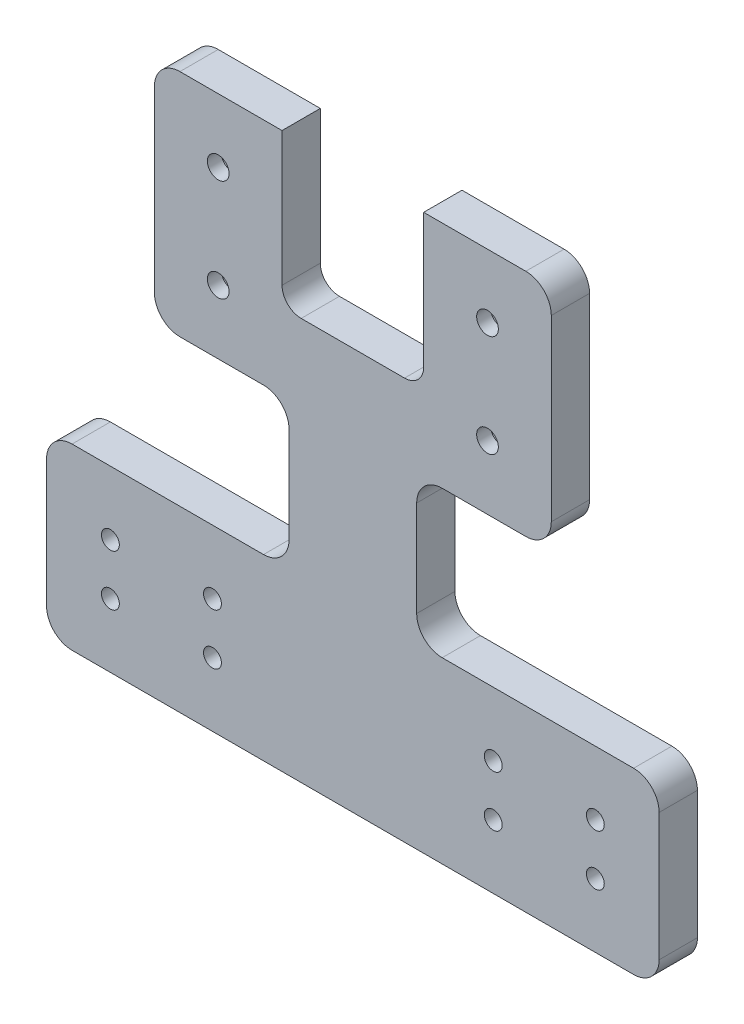
SolidWorks part; units mm, degrees
ref_plane "Front Plane" through (0, 0, 0) normal (0, 0, 1) x (1, 0, 0)
ref_plane "Top Plane" through (0, 0, 0) normal (0, 1, 0) x (1, 0, 0)
ref_plane "Right Plane" through (0, 0, 0) normal (1, 0, 0) x (0, 0, -1)
sketch "Sketch1" plane through (0, 0, 0) normal (0, 0, 1) x (1, 0, 0)
  line L0 (28.1, 15) -> (-28.1, 15) construction
  line L1 (-28.1, -15) -> (28.1, 15) construction
  line L2 (-28.1, 15) -> (-28.1, -15) construction
  line L3 (-28.1, -15) -> (28.1, -15) construction
  line L4 (-50, 20) -> (50, 20)
  line L5 (28.1, 15) -> (28.1, -15) construction
  line L6 (-50, 20) -> (-50, -80)
  line L7 (-50, -80) -> (50, -80)
  line L8 (50, 20) -> (50, -80)
  line L9 (-28.1, 15) -> (28.1, -15) construction
  line L10 (-50, 20) -> (50, -80) construction
  line L12 (-50, -80) -> (50, 20) construction
  dimension "D4" = 30
  dimension "D5" = 50
  dimension "D2" = 50
  dimension "D1" = 20
  dimension "D3" = 56.2
  dimension "D6" = 80
extrude "Boss-Extrude1" add sketch "Sketch1" along normal blind 6
sketch "Sketch2" plane through (0, 0, 0) normal (0, 0, 1) x (1, 0, 0)
  line L0 (28.1, 15) -> (-28.1, 15) construction
  line L1 (-28.1, -15) -> (28.1, 15) construction
  line L2 (-28.1, 15) -> (-28.1, -15) construction
  line L3 (-28.1, -15) -> (28.1, -15) construction
  line L4 (28.1, 15) -> (28.1, -15) construction
  line L5 (-28.1, 15) -> (28.1, -15) construction
  line L6 (-28.1, 0) -> (28.1, 0) construction
  line L14 (0, 15) -> (0, -15) construction
  circle A0 centre (21.1, -8) radius 2.9
  circle A1 centre (-21.1, 8) radius 2.9
  circle A2 centre (-21.1, -8) radius 2.9
  circle A4 centre (21.1, 8) radius 2.9
  dimension "D4" = 5.8
  dimension "D1" = 56.2
  dimension "D2" = 30
  dimension "D5" = 8
  dimension "D6" = 21.1
extrude "Cut-Extrude1" cut sketch "Sketch2" along normal blind 3.8
sketch "Sketch3" plane through (0, 0, 0) normal (0, 0, -1) x (-1, 0, 0)
  line L0 (28.1, 15) -> (-28.1, 15) construction
  line L1 (-28.1, -15) -> (28.1, 15) construction
  line L2 (-28.1, 15) -> (-28.1, -15) construction
  line L3 (-28.1, -15) -> (28.1, -15) construction
  line L4 (28.1, 15) -> (28.1, -15) construction
  line L5 (-28.1, 15) -> (28.1, -15) construction
  line L6 (-28.1, 0) -> (28.1, 0) construction
  line L7 (-17.9015, 8) -> (-19.5007, 10.77) construction
  line L8 (-19.5007, 10.77) -> (-22.6993, 10.77) construction
  line L9 (-22.6993, 10.77) -> (-24.2985, 8) construction
  line L10 (-24.2985, 8) -> (-22.6993, 5.23) construction
  line L11 (-22.6993, 5.23) -> (-19.5007, 5.23) construction
  line L12 (-19.5007, 5.23) -> (-17.9015, 8) construction
  line L13 (19.5007, 5.23) -> (17.9015, 8) construction
  line L14 (0, 15) -> (0, -15) construction
  line L15 (22.6993, 5.23) -> (19.5007, 5.23) construction
  line L16 (24.2985, 8) -> (22.6993, 5.23) construction
  line L17 (22.6993, 10.77) -> (24.2985, 8) construction
  line L18 (19.5007, 10.77) -> (22.6993, 10.77) construction
  line L19 (17.9015, 8) -> (19.5007, 10.77) construction
  line L20 (17.9015, -8) -> (19.5007, -10.77) construction
  line L21 (19.5007, -10.77) -> (22.6993, -10.77) construction
  line L22 (22.6993, -10.77) -> (24.2985, -8) construction
  line L23 (24.2985, -8) -> (22.6993, -5.23) construction
  line L24 (22.6993, -5.23) -> (19.5007, -5.23) construction
  line L25 (19.5007, -5.23) -> (17.9015, -8) construction
  line L26 (-19.5007, -5.23) -> (-17.9015, -8) construction
  line L27 (-22.6993, -5.23) -> (-19.5007, -5.23) construction
  line L28 (-24.2985, -8) -> (-22.6993, -5.23) construction
  line L29 (-22.6993, -10.77) -> (-24.2985, -8) construction
  line L30 (-19.5007, -10.77) -> (-22.6993, -10.77) construction
  line L31 (-17.9015, -8) -> (-19.5007, -10.77) construction
  circle A0 centre (-21.1, 8) radius 2.77 construction
  circle A1 centre (21.1, 8) radius 2.77 construction
  circle A2 centre (21.1, -8) radius 2.77 construction
  circle A3 centre (-21.1, -8) radius 2.77 construction
  circle A4 centre (-21.1, 8) radius 1.7
  circle A5 centre (21.1, 8) radius 1.7
  circle A6 centre (21.1, -8) radius 1.7
  circle A7 centre (-21.1, -8) radius 1.7
  dimension "D3" = 5.54
  dimension "D4" = 3.4
  dimension "D1" = 56.2
  dimension "D2" = 30
extrude "Cut-Extrude2" cut sketch "Sketch3" against normal up to surface (6 mm away) up to face at (0, -30, 6)
sketch "Sketch4" plane through (0, 0, 0) normal (0, 0, -1) x (-1, 0, 0)
  line L0 (-30, -29) -> (-30, -51) construction
  line L1 (0, 0) -> (0, -80) construction
  line L2 (50, -80) -> (-50, -80) construction
  line L3 (-38, -59) -> (-38, -51) construction
  line L4 (-22, -59) -> (-22, -51) construction
  line L5 (0, -40) -> (24.6, -40) construction
  line L6 (-10, -65) -> (-50, -65) construction
  line L7 (-10, -65) -> (-10, -15) construction
  line L8 (-10, -15) -> (-50, -15) construction
  line L9 (-50, -65) -> (-50, -15) construction
  line L10 (-10, -65) -> (-50, -15) construction
  line L11 (-10, -15) -> (-50, -65) construction
  line L12 (38, -59) -> (38, -51) construction
  line L13 (30, -59) -> (30, -51) construction
  line L14 (22, -59) -> (22, -51) construction
  circle A0 centre (-38, -59) radius 2.3
  circle A1 centre (-38, -51) radius 2.3
  circle A2 centre (-22, -51) radius 2.3
  circle A3 centre (-22, -59) radius 2.3
  circle A4 centre (38, -59) radius 2.3
  circle A5 centre (22, -51) radius 2.3
  circle A6 centre (22, -59) radius 2.3
  circle A7 centre (38, -51) radius 2.3
  point P14 (-30, -40)
  point P32 (30, -55)
  dimension "D1" = 4.6
  dimension "D8" = 24.6
  dimension "D9" = 4.6
  dimension "D2" = 50
  dimension "D3" = 8
  dimension "D4" = 8
  dimension "D5" = 40
  dimension "D6" = 10
  dimension "D7" = 15
  dimension "D10" = 22
  dimension "D11" = 8
  dimension "D12" = 22
extrude "Cut-Extrude3" cut sketch "Sketch4" against normal blind 2.5
sketch "Sketch5" plane through (0, 0, 0) normal (0, 0, -1) x (-1, 0, 0)
  line L0 (-30, -59) -> (-30, -51) construction
  line L1 (-38, -59) -> (-38, -51) construction
  line L2 (-22, -59) -> (-22, -51) construction
  line L3 (0, 0) -> (0, -55) construction
  line L6 (-30, -59) -> (-30, -51) construction
  line L7 (-38, -59) -> (-38, -51) construction
  line L8 (-22, -59) -> (-22, -51) construction
  line L9 (0, -55) -> (24.6, -55) construction
  line L10 (38, -59) -> (38, -51) construction
  line L11 (30, -59) -> (30, -51) construction
  line L12 (22, -59) -> (22, -51) construction
  circle A0 centre (-38, -59) radius 1.4
  circle A1 centre (-38, -51) radius 1.4
  circle A2 centre (-22, -51) radius 1.4
  circle A3 centre (-22, -59) radius 1.4
  circle A8 centre (-38, -59) radius 2.8 construction
  circle A9 centre (-38, -51) radius 2.8 construction
  circle A10 centre (-22, -51) radius 2.8 construction
  circle A11 centre (-22, -59) radius 2.8 construction
  circle A12 centre (38, -59) radius 1.4
  circle A13 centre (22, -51) radius 1.4
  circle A14 centre (22, -59) radius 1.4
  circle A15 centre (38, -51) radius 1.4
  point P10 (-30, -55)
  point P32 (-30, -55)
  point P45 (30, -55)
  dimension "D1" = 2.8
  dimension "D2" = 5.6
  dimension "D4" = 2.8
  dimension "D3" = 8
  dimension "D5" = 8
  dimension "D6" = 22
  dimension "D7" = 22
extrude "Cut-Extrude4" cut sketch "Sketch5" against normal up to surface (6 mm away) up to face at (-19.4, 8, 6)
sketch "Sketch6" plane through (0, 0, 6) normal (0, 0, 1) x (1, 0, 0)
  line L0 (0, 20) -> (0, -80) construction
  line L1 (50, 20) -> (-50, 20) construction
  line L2 (-50, -80) -> (50, -80) construction
  line L3 (-31.1, -14) -> (-31.1, 14)
  line L4 (-27.1, 18) -> (27.1, 18)
  line L5 (-27.1, -18) -> (-14, -18)
  line L6 (-10, -22) -> (-10, -37)
  line L7 (-14, -41) -> (-44, -41)
  line L8 (-48, -45) -> (-48, -65)
  line L9 (-44, -69) -> (44, -69)
  line L10 (14, -41) -> (44, -41)
  line L11 (48, -65) -> (48, -45)
  line L12 (10, -22) -> (10, -37)
  line L13 (27.1, -18) -> (14, -18)
  line L14 (31.1, -14) -> (31.1, 14)
  line L16 (-50, 20) -> (50, 20)
  line L17 (-50, 20) -> (-50, -80)
  line L18 (-50, -80) -> (50, -80)
  line L19 (50, 20) -> (50, -80)
  circle A1 centre (-21.1, -8) radius 1.7 construction
  circle A2 centre (-22, -51) radius 1.4 construction
  circle A3 centre (-38, -51) radius 1.4 construction
  circle A4 centre (-38, -59) radius 1.4 construction
  circle A5 centre (-21.1, 8) radius 1.7 construction
  circle A6 centre (38, -51) radius 1.4 construction
  arc A7 (27.1, 18) -> (31.1, 14) centre (27.1, 14) cw
  arc A8 (31.1, -14) -> (27.1, -18) centre (27.1, -14) cw
  arc A9 (14, -18) -> (10, -22) centre (14, -22) ccw
  arc A10 (10, -37) -> (14, -41) centre (14, -37) ccw
  arc A11 (44, -41) -> (48, -45) centre (44, -45) cw
  arc A12 (48, -65) -> (44, -69) centre (44, -65) cw
  arc A13 (-44, -69) -> (-48, -65) centre (-44, -65) cw
  arc A14 (-48, -45) -> (-44, -41) centre (-44, -45) cw
  arc A15 (-14, -41) -> (-10, -37) centre (-14, -37) ccw
  arc A16 (-10, -22) -> (-14, -18) centre (-14, -22) ccw
  arc A17 (-27.1, -18) -> (-31.1, -14) centre (-27.1, -14) cw
  arc A18 (-31.1, 14) -> (-27.1, 18) centre (-27.1, 14) cw
  point P25 (0, -69)
  point P30 (0, 18)
  point P40 (31.1, 18)
  point P43 (31.1, -18)
  point P46 (10, -18)
  point P49 (10, -41)
  point P52 (48, -41)
  point P57 (-48, -69)
  point P60 (-48, -41)
  point P63 (-10, -41)
  point P66 (-10, -18)
  point P69 (-31.1, -18)
  point P72 (-31.1, 18)
  dimension "D1" = 10
  dimension "D2" = 10
  dimension "D4" = 10
  dimension "D5" = 10
  dimension "D6" = 10
  dimension "D8" = 10
  dimension "D9" = 4
  dimension "D3" = 10
  dimension "D7" = 10
extrude "Cut-Extrude5" cut sketch "Sketch6" against normal blind 10
sketch "Sketch7" plane through (0, 0, 0) normal (0, 0, 1) x (1, 0, 0)
  line L0 (-11.1, 8) -> (-31.1, 8) construction
  line L1 (-31.1, 14) -> (-31.1, -14) construction
  line L2 (-21.1, 8) -> (-21.1, -8) construction
  line L3 (-11.1, 18) -> (-11.1, -3)
  line L4 (27.1, 18) -> (-27.1, 18) construction
  line L5 (-8.1, -6) -> (8.1, -6)
  line L6 (-11.1, 18) -> (11.1, 18)
  line L7 (0, 18) -> (0, -6) construction
  line L8 (11.1, 18) -> (11.1, -3)
  arc A0 (-8.1, -6) -> (-11.1, -3) centre (-8.1, -3) cw
  arc A1 (8.1, -6) -> (11.1, -3) centre (8.1, -3) ccw
  point P16 (-11.1, -6)
  point P22 (11.1, -6)
  dimension "D2" = 3
  dimension "D1" = 6
extrude "Cut-Extrude6" cut sketch "Sketch7" along normal up to next
